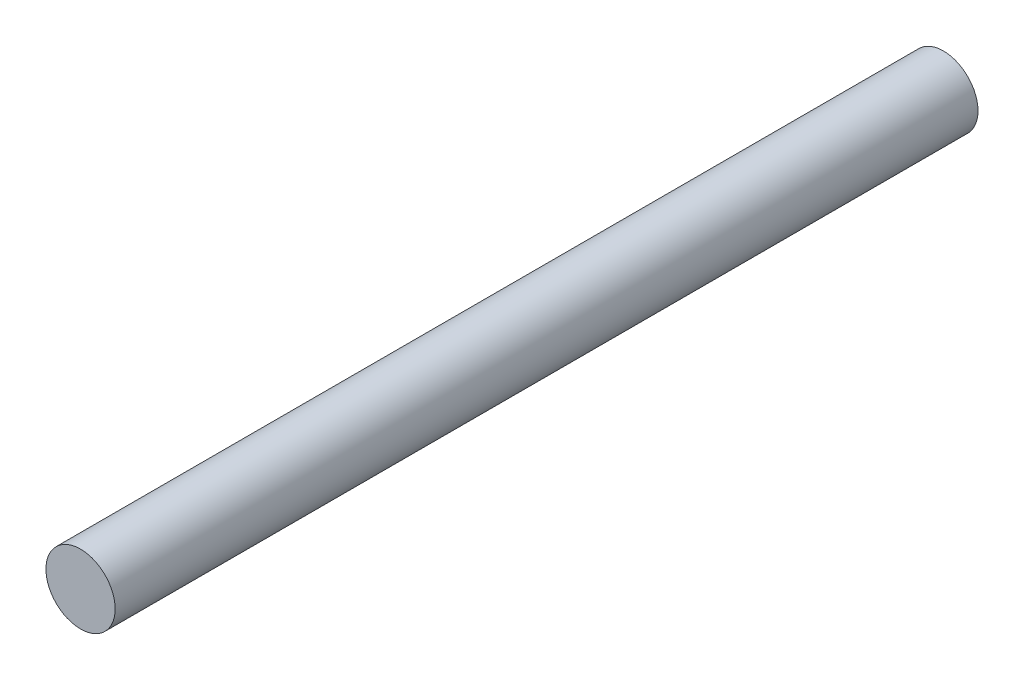
SolidWorks part; units mm, degrees
ref_plane "Plan de face" through (0, 0, 0) normal (0, 0, 1) x (1, 0, 0)
ref_plane "Plan de dessus" through (0, 0, 0) normal (0, 1, 0) x (1, 0, 0)
ref_plane "Plan de droite" through (0, 0, 0) normal (1, 0, 0) x (0, 0, -1)
sketch "Esquisse1" plane through (0, 0, 0) normal (0, 0, 1) x (1, 0, 0)
  circle A0 centre (0, 0) radius 22.86
  dimension "D1" = 45.72
extrude "Boss.-Extru.1" add sketch "Esquisse1" along normal mid plane 570
